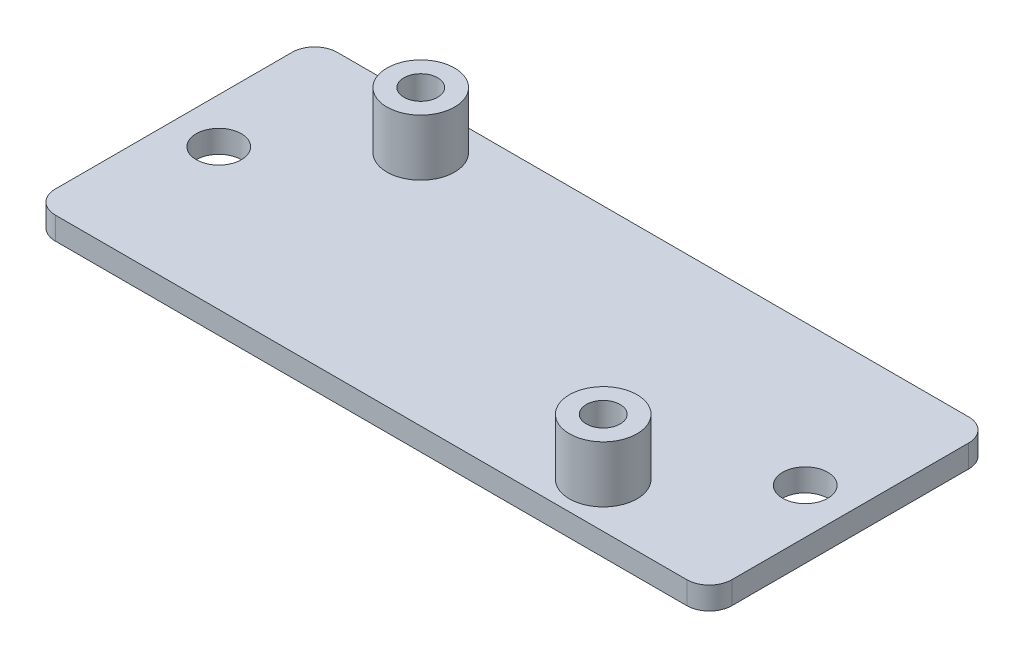
SolidWorks part; units mm, degrees
material "ABS"
ref_plane "Спереди" through (0, 0, 0) normal (0, 0, 1) x (1, 0, 0)
ref_plane "Сверху" through (0, 0, 0) normal (0, 1, 0) x (1, 0, 0)
ref_plane "Справа" through (0, 0, 0) normal (1, 0, 0) x (0, 0, -1)
sketch "Эскиз1" plane through (0, 0, 0) normal (0, 1, 0) x (1, 0, 0)
  line L1 (0, 0) -> (60, 0)
  line L2 (0, 0) -> (0, -25)
  line L3 (0, -25) -> (60, -25)
  line L4 (60, 0) -> (60, -25)
  dimension "D1" = 25
  dimension "D2" = 60
extrude "Бобышка-Вытянуть1" add sketch "Эскиз1" along normal blind 2
sketch "Эскиз2" plane through (0, 2, 0) normal (0, 1, 0) x (1, 0, 0)
  line L0 (0, 0) -> (0, -25) construction
  line L1 (60, -25) -> (60, 0) construction
  line L2 (60, 0) -> (0, 0) construction
  line L3 (0, -25) -> (60, -25) construction
  circle A0 centre (13.41, -4) radius 3
  circle A1 centre (46.59, -21) radius 3
  dimension "D2" = 13.41
  dimension "D4" = 4
  dimension "D5" = 6
  dimension "D6" = 6
  dimension "D1" = 13.41
  dimension "D3" = 4
extrude "Бобышка-Вытянуть2" add sketch "Эскиз2" along normal blind 5
sketch "Эскиз3" plane through (0, 7, 0) normal (0, 1, 0) x (1, 0, 0)
  circle A0 centre (13.41, -4) radius 1.5
  circle A1 centre (46.59, -21) radius 1.5
  dimension "D1" = 3
  dimension "D2" = 3
extrude "Вырез-Вытянуть1" cut sketch "Эскиз3" against normal through all both and the other way through all
sketch "Эскиз4" plane through (0, 2, 0) normal (0, 1, 0) x (1, 0, 0)
  line L0 (0, -12.5) -> (60, -12.5) construction
  line L1 (0, 0) -> (0, -25) construction
  line L2 (60, -25) -> (60, 0) construction
  circle A0 centre (4, -12.5) radius 2
  circle A1 centre (56, -12.5) radius 2
  dimension "D1" = 4
  dimension "D2" = 4
  dimension "D3" = 4
  dimension "D4" = 4
extrude "Вырез-Вытянуть2" cut sketch "Эскиз4" against normal through all both and the other way through all
fillet "Скругление1" radius 2 1 edges at (0, 1, 0) type face fillet first side face at (30, 1, 0) second side face at (0, 1, 12.5)
fillet "Скругление2" radius 2 1 edges at (0, 1, 25) type face fillet first side face at (0, 1, 13.5) second side face at (30, 1, 25)
fillet "Скругление3" radius 2 1 edges at (60, 1, 25) type face fillet first side face at (31, 1, 25) second side face at (60, 1, 12.5)
fillet "Скругление4" radius 2 1 edges at (60, 1, 0) type face fillet first side face at (60, 1, 11.5) second side face at (31, 1, 0)
